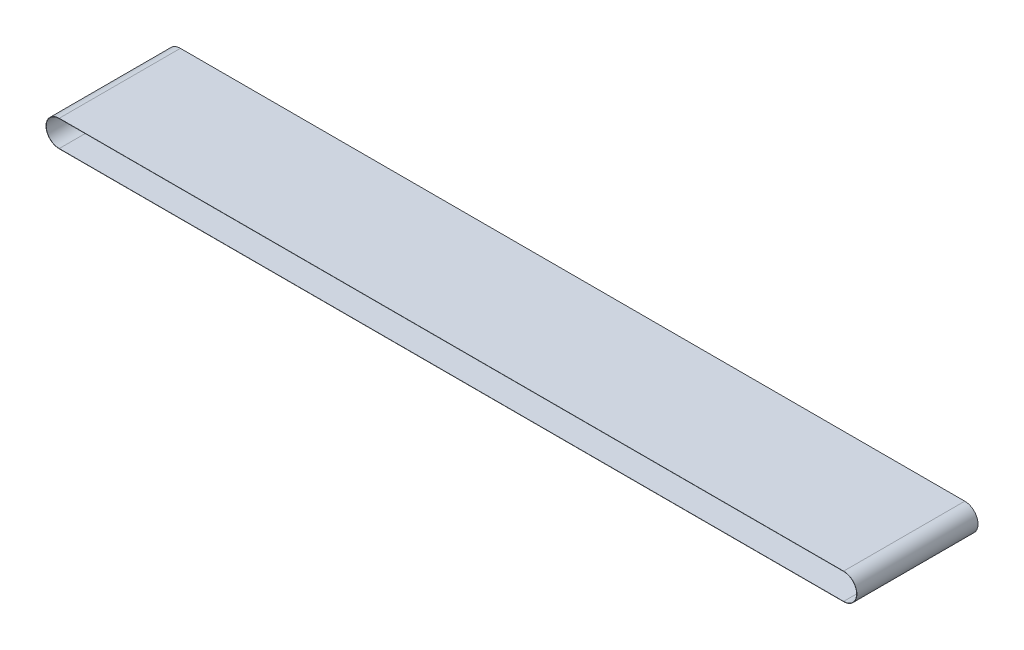
SolidWorks part; units mm, degrees
ref_plane "Front" through (0, 0, 0) normal (0, 0, 1) x (1, 0, 0)
ref_plane "Top" through (0, 0, 0) normal (0, 1, 0) x (1, 0, 0)
ref_plane "Right" through (0, 0, 0) normal (1, 0, 0) x (0, 0, -1)
sketch "草图2" plane through (0, 0, 0) normal (0, 0, 1) x (1, 0, 0)
  line L0 (0, 0) -> (1, 0) construction
  line L1 (0, 0) -> (0, 1) construction
  line L2 (0, -165) -> (-9873.2761, -165)
  line L3 (-9873.2761, 165) -> (0, 165)
  arc A0 (0, 165) -> (0, -165) centre (0, 0) cw
  arc A1 (-9873.2761, -165) -> (-9873.2761, 165) centre (-9873.2761, 0) cw
sketch "草图3" plane through (0, 0, 0) normal (1, 0, 0) x (0, 0, -1)
  line L1 (-762.5, 166.5) -> (762.5, 166.5)
  line L2 (-762.5, 166.5) -> (-762.5, 163.5)
  line L3 (-762.5, 163.5) -> (762.5, 163.5)
  line L4 (762.5, 166.5) -> (762.5, 163.5)
  line L5 (-762.5, 166.5) -> (762.5, 163.5) construction
  line L6 (-762.5, 163.5) -> (762.5, 166.5) construction
  point P0 (0, 165)
  point P5 (0, 0)
  point P6 (0, 166.5)
  point P7 (0, 0)
  point P9 (0, 0)
  dimension "D1" = 1525
  dimension "D2" = 3
sweep "扫描1" add profiles "草图3" path "草图2"
